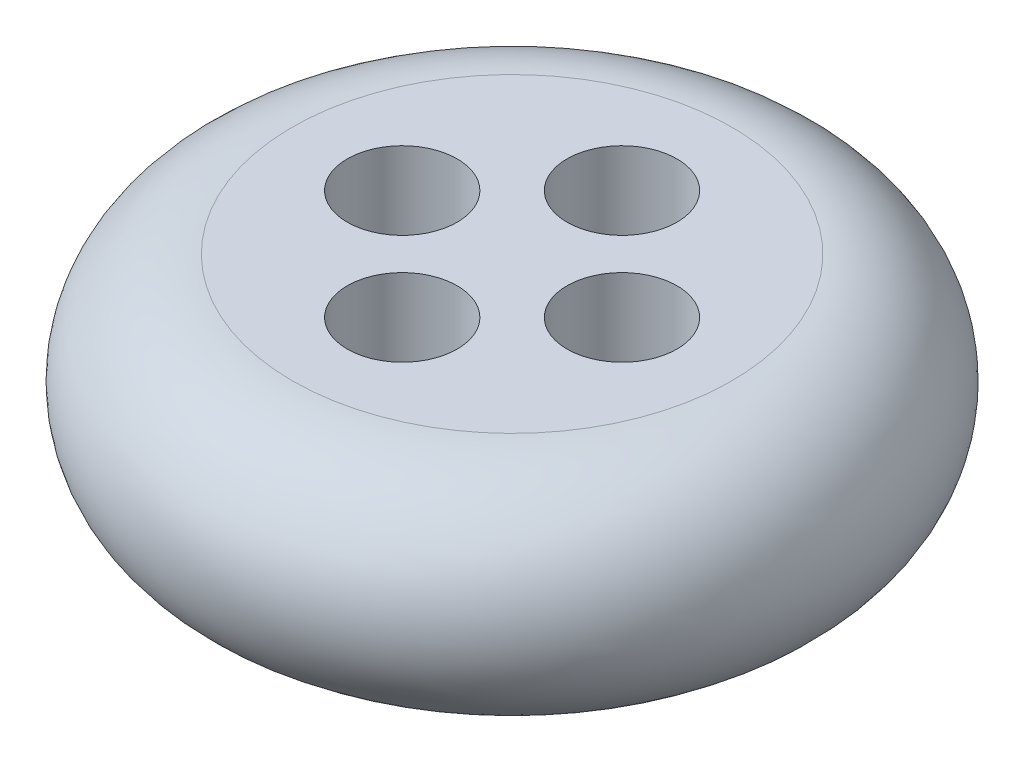
SolidWorks part; units mm, degrees
ref_plane "前视基准面" through (0, 0, 0) normal (0, 0, 1) x (1, 0, 0)
ref_plane "上视基准面" through (0, 0, 0) normal (0, 1, 0) x (1, 0, 0)
ref_plane "右视基准面" through (0, 0, 0) normal (1, 0, 0) x (0, 0, -1)
other "Configuration Table"
sketch "草图1" plane through (0, 0, 0) normal (0, 1, 0) x (1, 0, 0)
  circle A0 centre (0, 0) radius 15
  circle A1 centre (0, 5) radius 2.5
  circle A2 centre (0, -5) radius 2.5
  circle A3 centre (5, 0) radius 2.5
  circle A4 centre (-5, 0) radius 2.5
  dimension "D1" = 30
  dimension "D2" = 5
  dimension "D3" = 5
  dimension "D4" = 5
  dimension "D5" = 5
  dimension "D6" = 5
extrude "凸台-拉伸1" add sketch "草图1" along normal blind 10
fillet "圆角1" 2 edges at (0, 10, 15) (0, 0, 15) type full round first side face at (5, 10, 2.5) second side face at (0, 0, 15) middle face at (0, 10, 15)
